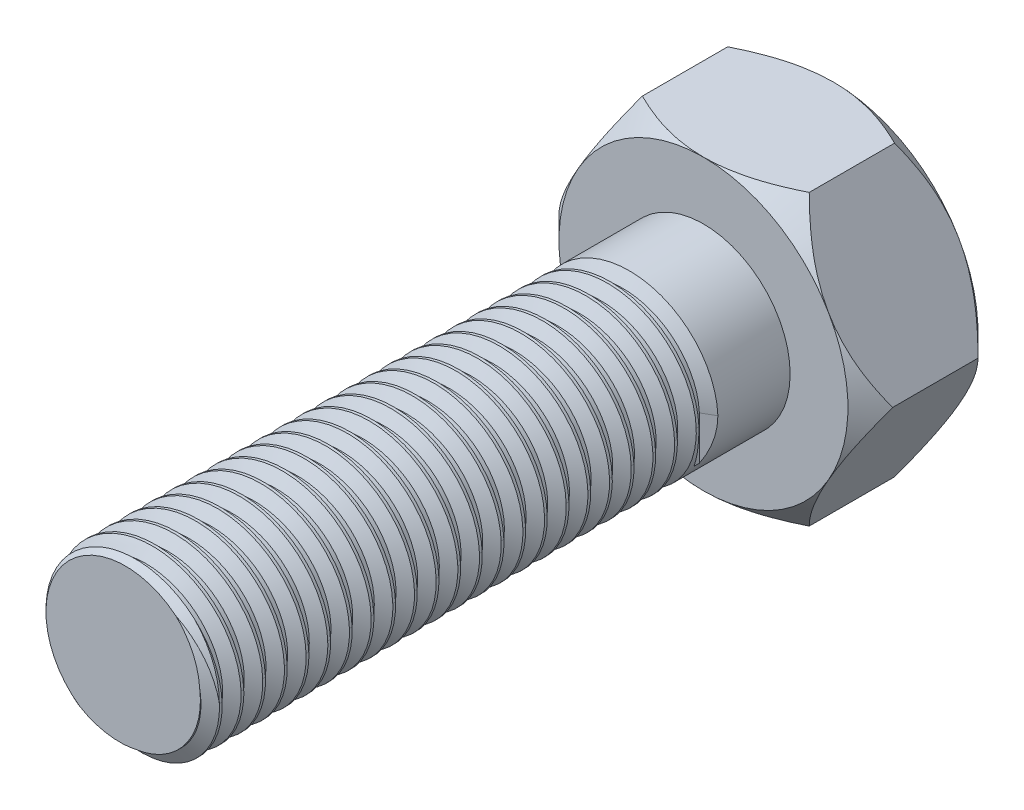
SolidWorks part; units mm, degrees
ref_plane "Front Plane" through (0, 0, 0) normal (0, 0, 1) x (1, 0, 0)
ref_plane "Top Plane" through (0, 0, 0) normal (0, 1, 0) x (1, 0, 0)
ref_plane "Right Plane" through (0, 0, 0) normal (1, 0, 0) x (0, 0, -1)
sketch "Sketch1" plane through (0, 0, 0) normal (0, 0, 1) x (1, 0, 0)
  line L1 (11.547, 0) -> (5.7735, 10)
  line L2 (5.7735, 10) -> (-5.7735, 10)
  line L3 (-5.7735, 10) -> (-11.547, 0)
  line L4 (-11.547, 0) -> (-5.7735, -10)
  line L5 (-5.7735, -10) -> (5.7735, -10)
  line L6 (5.7735, -10) -> (11.547, 0)
  circle A0 centre (0, 0) radius 10 construction
  dimension "D1" = 20
extrude "Boss-Extrude1" add sketch "Sketch1" along normal mid plane 9
sketch "Sketch2" plane through (0, 0, 4.5) normal (0, 0, 1) x (1, 0, 0)
  line L0 (5.7735, -10) -> (11.547, 0) construction
  circle A0 centre (0, 0) radius 10
extrude "Cut-Extrude1" cut sketch "Sketch2" against normal blind 9 draft 45 flip side to cut
mirror "Mirror1" about plane through (0, 0, 0) normal (0, 0, 1) of "Cut-Extrude1"
sketch "Sketch3" plane through (0, 0, 4.5) normal (0, 0, 1) x (1, 0, 0)
  circle A0 centre (0, 0) radius 6
  dimension "D1" = 12
extrude "Boss-Extrude2" add sketch "Sketch3" along normal blind 40
chamfer "Chamfer1" distance 0.5 angle 45 1 edges at (6, 0, 44.5)
thread "Thread1" pitch 1.5 method cut profile "Thread Profile1" start angle 0, offset 5, length 0, pitch 1.5, diameter 12
ref_plane "Plane1" through (6, 0, 9.5) normal (0, -1, 0) x (1, 0, 0)
sketch "Thread Profile1" plane through (6, 0, 9.5) normal (0, -1, 0) x (1, 0, 0)
  line L0 (0, 0) -> (0, 1.5) construction
  line L11 (0, 0) -> (0, 1.3125)
  line L12 (0, 1.3125) -> (-0.8119, 0.8437)
  line L13 (-0.8119, 0.8437) -> (-0.8119, 0.4687)
  line L15 (-0.8119, 0.4687) -> (0, 0)
  line L17 (-0.8119, 0.6562) -> (0, 0.6562) construction
  point P2 (0, 0)
  dimension "Pitch" = 1.5
  dimension "Profile_Angle" = 60
  dimension "Profile_Land" = 0.375
  dimension "Profile_Height" = 0.8119
sketch "Sketch9" plane through (0, 0, 0) normal (0, 1, 0) x (1, 0, 0)
  line L4 (6, -9.5) -> (5.1881, -9.9687)
  line L5 (5.1881, -9.9687) -> (5.1881, -10.3437)
  line L6 (5.1881, -10.3437) -> (6, -10.8125)
  line L7 (6, -10.8125) -> (6, -9.5)
  line L8 (6, -9.5) -> (5.1881, -9.9687)
  line L9 (5.1881, -9.9687) -> (5.1881, -10.3437)
  line L10 (5.1881, -10.3437) -> (6, -10.8125)
  line L11 (6, -10.8125) -> (6, -9.5)
  dimension "D1" = 0
extrude "Cut-Extrude2" cut sketch "Sketch9" against normal through all
